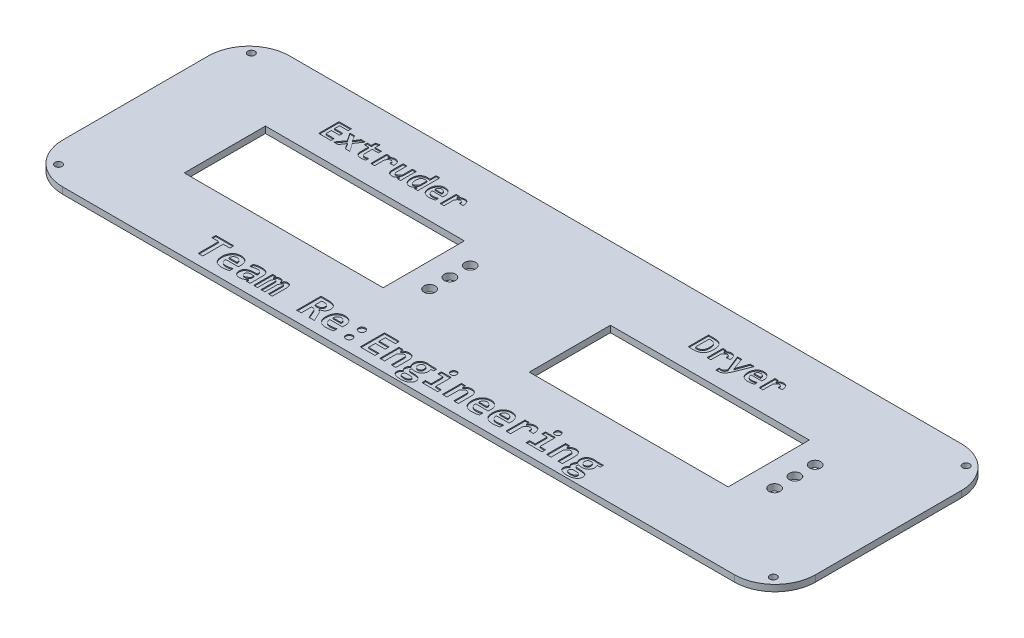
SolidWorks part; units mm, degrees
ref_plane "Front" through (0, 0, 0) normal (0, 0, 1) x (1, 0, 0)
ref_plane "Top" through (0, 0, 0) normal (0, 1, 0) x (1, 0, 0)
ref_plane "Right" through (0, 0, 0) normal (1, 0, 0) x (0, 0, -1)
sketch "Sketch1" plane through (0, 0, 0) normal (0, 1, 0) x (1, 0, 0)
  line L1 (-185.5, 55.9) -> (185.5, 55.9)
  line L2 (-185.5, 55.9) -> (-185.5, -55.9)
  line L3 (-185.5, -55.9) -> (185.5, -55.9)
  line L4 (185.5, 55.9) -> (185.5, -55.9)
  line L5 (-185.5, 55.9) -> (185.5, -55.9) construction
  line L6 (-185.5, -55.9) -> (185.5, 55.9) construction
  point P0 (0, 0)
  dimension "D1" = 111.8
  dimension "D2" = 371
extrude "Boss-Extrude1" add sketch "Sketch1" along normal blind 3.175
fillet "Fillet1" radius 20 4 edges at (-185.5, 1.5875, -55.9) (-185.5, 1.5875, 55.9) (185.5, 1.5875, -55.9) (185.5, 1.5875, 55.9)
sketch "Sketch2" plane through (0, 3.175, 0) normal (0, 1, 0) x (1, 0, 0)
  line L0 (0, 55.9) -> (0, -55.9) construction
  line L1 (165.5, 55.9) -> (-165.5, 55.9) construction
  line L2 (-165.5, -55.9) -> (165.5, -55.9) construction
  line L3 (0, 0) -> (-85, 0) construction
  line L4 (-85, 35) -> (-85, 0) construction
  line L5 (-152.5, -35) -> (-17.5, -35) construction
  line L6 (-152.5, -35) -> (-152.5, 35) construction
  line L7 (-152.5, 35) -> (-17.5, 35) construction
  line L8 (-17.5, -35) -> (-17.5, 35) construction
  line L9 (-152.5, -35) -> (-17.5, 35) construction
  line L10 (-152.5, 35) -> (-17.5, -35) construction
  line L11 (-85, 0) -> (-152.5, 0) construction
  line L12 (152.5, -35) -> (152.5, 35) construction
  line L13 (-141.5, -20) -> (-43.5, -20)
  line L14 (-141.5, -20) -> (-141.5, 20)
  line L15 (-141.5, 20) -> (-43.5, 20)
  line L16 (-43.5, -20) -> (-43.5, 20)
  line L17 (-141.5, -20) -> (-43.5, 20) construction
  line L18 (-141.5, 20) -> (-43.5, -20) construction
  line L19 (152.5, -35) -> (17.5, -35) construction
  line L20 (17.5, -35) -> (17.5, 35) construction
  line L21 (152.5, 35) -> (17.5, 35) construction
  line L23 (28.5, 20) -> (126.5, 20)
  line L24 (28.5, 20) -> (28.5, -20)
  line L25 (28.5, -20) -> (126.5, -20)
  line L26 (126.5, 20) -> (126.5, -20)
  line L27 (28.5, 20) -> (126.5, -20) construction
  line L28 (28.5, -20) -> (126.5, 20) construction
  point P31 (-92.5, 0)
  point P40 (77.5, 0)
  dimension "D1" = 135
  dimension "D2" = 70
  dimension "D3" = 85
  dimension "D7" = 60
  dimension "D8" = 35
  dimension "D9" = 40
  dimension "D10" = 98
  dimension "D11" = 60
  dimension "D12" = 35
  dimension "D13" = 40
  dimension "D14" = 98
extrude "Cut-Extrude1" cut sketch "Sketch2" against normal up to next
sketch "Sketch6" plane through (0, 3.175, 0) normal (0, 1, 0) x (1, 0, 0)
  circle A0 centre (176.1066, -47.3372) radius 2.5 construction
  circle A1 centre (176.1066, -47.3372) radius 2.5 construction
  circle A2 centre (-176.1066, -47.3372) radius 2.5 construction
  circle A3 centre (-176.1066, -47.3372) radius 2.5 construction
  circle A4 centre (-176.1066, 47.6638) radius 2.5 construction
  circle A5 centre (-176.1066, 47.6638) radius 2.5 construction
  circle A6 centre (176.1066, 47.6638) radius 2.5 construction
  circle A7 centre (176.1066, 47.6638) radius 2.5 construction
  circle A8 centre (176.1066, 47.6638) radius 1.75
  circle A9 centre (-176.1066, 47.6638) radius 1.75
  circle A10 centre (-176.1066, -47.3372) radius 1.75
  circle A11 centre (176.1066, -47.3372) radius 1.75
  dimension "D1" = 3.5
extrude "Cut-Extrude2" cut sketch "Sketch6" against normal up to next
sketch "Sketch11" plane through (0, 3.175, 0) normal (0, 1, 0) x (1, 0, 0)
  line L5 (-43.5, 30) -> (-141.5, 30)
  line L6 (-43.5, 30) -> (-141.5, 30) construction
  line L8 (126.5, 30) -> (28.5, 30)
  line L9 (126.5, 30) -> (28.5, 30) construction
  text T0 "Extruder" font "Consolas" height 10
  text T1 "Dryer" font "Consolas" height 10
  dimension "D1" = 10
  dimension "D2" = 10
extrude "Cut-Extrude4" cut sketch "Sketch11" against normal blind 0.5
sketch "Sketch12" plane through (0, 3.175, 0) normal (0, 1, 0) x (1, 0, 0)
  line L2 (-165.5, -50.9) -> (165.5, -50.9)
  line L3 (-165.5, -50.9) -> (165.5, -50.9) construction
  text T0 "Team Re:Engineering  " font "Consolas" height 12
  dimension "D1" = 5
extrude "Cut-Extrude5" cut sketch "Sketch12" against normal blind 0.5
sketch "Sketch13" plane through (0, 3.175, 0) normal (0, 1, 0) x (1, 0, 0)
  line L0 (-31.5, 55.9) -> (-31.5, 10.9) construction
  line L1 (165.5, 55.9) -> (-165.5, 55.9) construction
  line L2 (-31.5, 10.9) -> (-31.5, 0.9) construction
  line L3 (-31.5, 0.9) -> (-31.5, -9.1) construction
  line L4 (-31.5, -9.1) -> (-31.5, -55.9) construction
  line L5 (-165.5, -55.9) -> (165.5, -55.9) construction
  line L6 (-43.5, -20) -> (-43.5, 20) construction
  circle A0 centre (-31.5, 10.9) radius 2.75
  circle A1 centre (-31.5, 0.9) radius 2.75
  circle A2 centre (-31.5, -9.1) radius 2.75
  circle A3 centre (138.5, 10.9) radius 2.75
  circle A4 centre (138.5, 0.9) radius 2.75
  circle A5 centre (138.5, -9.1) radius 2.75
  dimension "D1" = 10
  dimension "D2" = 5.5
  dimension "D3" = 12
  dimension "D4" = 45
  dimension "D5" = 2
extrude "Cut-Extrude6" cut sketch "Sketch13" against normal up to next
